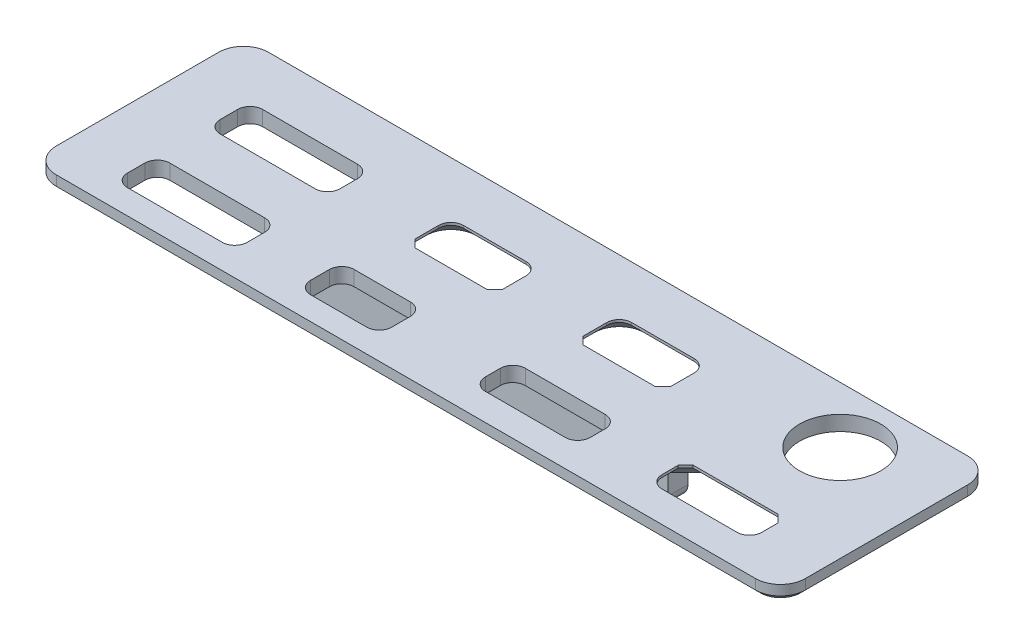
SolidWorks part; units mm, degrees
ref_plane "前视基准面" through (0, 0, 0) normal (0, 0, 1) x (1, 0, 0)
ref_plane "上视基准面" through (0, 0, 0) normal (0, 1, 0) x (1, 0, 0)
ref_plane "右视基准面" through (0, 0, 0) normal (1, 0, 0) x (0, 0, -1)
sketch "草图1" plane through (0, 0, 0) normal (0, 1, 0) x (1, 0, 0)
  line L1 (-30, 8.5) -> (30, 8.5)
  line L2 (-30, 8.5) -> (-30, -8.5)
  line L3 (-30, -8.5) -> (30, -8.5)
  line L4 (30, 8.5) -> (30, -8.5)
  line L5 (-30, 8.5) -> (30, -8.5) construction
  line L6 (-30, -8.5) -> (30, 8.5) construction
  point P0 (0, 0)
  dimension "D1" = 60
  dimension "D2" = 17
extrude "凸台-拉伸1" add sketch "草图1" along normal blind 1.2
sketch "草图4" plane through (0, 1.2, 0) normal (0, 1, 0) x (1, 0, 0)
  line L0 (-30, 8.5) -> (-30, -8.5) construction
  line L1 (-25.2717, 4.3) -> (-15.6717, 4.3)
  line L2 (-25.2717, 4.3) -> (-25.2717, 0.9)
  line L3 (-25.2717, 0.9) -> (-15.6717, 0.9)
  line L4 (-15.6717, 4.3) -> (-15.6717, 0.9)
  line L5 (-9.1829, 4.3) -> (-2.1829, 4.3)
  line L6 (-9.1829, 4.3) -> (-9.1829, 0.8)
  line L7 (-9.1829, 0.8) -> (-2.1829, 0.8)
  line L8 (-2.1829, 4.3) -> (-2.1829, 0.8)
  line L9 (4.2885, 4.3) -> (11.2885, 4.3)
  line L10 (4.2885, 4.3) -> (4.2885, 0.8)
  line L11 (4.2885, 0.8) -> (11.2885, 0.8)
  line L12 (11.2885, 4.3) -> (11.2885, 0.8)
  line L13 (17.05, -3.1348) -> (25.05, -3.1348)
  line L14 (17.05, -3.1348) -> (17.05, -6.0348)
  line L15 (17.05, -6.0348) -> (25.05, -6.0348)
  line L16 (25.05, -3.1348) -> (25.05, -6.0348)
  line L17 (3.2, -3.1348) -> (11.6, -3.1348)
  line L18 (3.2, -3.1348) -> (3.2, -6.3348)
  line L19 (3.2, -6.3348) -> (11.6, -6.3348)
  line L20 (11.6, -3.1348) -> (11.6, -6.3348)
  line L21 (-10.5, -3.1348) -> (-4, -3.1348)
  line L22 (-10.5, -3.1348) -> (-10.5, -6.6348)
  line L23 (-10.5, -6.6348) -> (-4, -6.6348)
  line L24 (-4, -3.1348) -> (-4, -6.6348)
  line L25 (-25.2717, -3.1348) -> (-15.6717, -3.1348)
  line L26 (-25.2717, -3.1348) -> (-25.2717, -6.5348)
  line L27 (-25.2717, -6.5348) -> (-15.6717, -6.5348)
  line L28 (-15.6717, -3.1348) -> (-15.6717, -6.5348)
  line L29 (30, 8.5) -> (-30, 8.5) construction
  line L31 (30, -8.5) -> (30, 8.5) construction
  line L32 (30, 8.5) -> (-30, 8.5) construction
  circle A0 centre (22.2985, 3.9832) radius 3.25
  dimension "D21" = 6.5
  dimension "D1" = 3.5
  dimension "D2" = 6.5
  dimension "D3" = 8.4
  dimension "D4" = 3.2
  dimension "D5" = 9.6
  dimension "D6" = 3.4
  dimension "D7" = 7
  dimension "D8" = 8
  dimension "D9" = 2.9
  dimension "D10" = 4.7283
  dimension "D11" = 7.6
  dimension "D12" = 11.6348
  dimension "D13" = 19.5
  dimension "D14" = 33.2
  dimension "D15" = 4.95
  dimension "D16" = 7
  dimension "D17" = 20.8171
  dimension "D18" = 34.2885
  dimension "D19" = 7.7015
  dimension "D20" = 4.5168
  dimension "D22" = 3.5
extrude "切除-拉伸1" cut sketch "草图4" against normal up to next
fillet "圆角2" radius 1 22 edges at (-25.2717, 0.6, -0.9) (-25.2717, 0.6, -4.3) (-15.6717, 0.6, -0.9) (-15.6717, 0.6, -4.3) (-2.1829, 0.6, -4.3) (-9.1829, 0.6, -4.3) (4.2885, 0.6, -4.3) (11.2885, 0.6, -4.3) (25.05, 0.6, 6.0348) (17.05, 0.6, 6.0348) (11.6, 0.6, 6.3348) (11.6, 0.6, 3.1348) (3.2, 0.6, 3.1348) (3.2, 0.6, 6.3348) (-4, 0.6, 6.6348) (-4, 0.6, 3.1348) (-10.5, 0.6, 3.1348) (-10.5, 0.6, 6.6348) (-15.6717, 0.6, 6.5348) (-15.6717, 0.6, 3.1348) (-25.2717, 0.6, 3.1348) (-25.2717, 0.6, 6.5348)
chamfer "倒角1" distance 0.6 angle 45 6 edges at (-9.1829, 0.6, -0.8) (-2.1829, 0.6, -0.8) (4.2885, 0.6, -0.8) (11.2885, 0.6, -0.8) (17.05, 0.6, 3.1348) (25.05, 0.6, 3.1348)
sketch "草图5" plane through (0, 0, 0) normal (0, -1, 0) x (1, 0, 0)
  line L0 (-30, -8.5) -> (-30, 8.5) construction
  line L1 (-13.9089, -3.3832) -> (-12.4089, -3.3832)
  line L2 (-13.9089, -3.3832) -> (-13.9089, 4.6168)
  line L3 (-13.9089, 4.6168) -> (-12.4089, 4.6168)
  line L4 (-12.4089, -3.3832) -> (-12.4089, 4.6168)
  line L5 (13.0911, -3.3832) -> (14.5911, -3.3832)
  line L6 (13.0911, -3.3832) -> (13.0911, 4.6168)
  line L7 (13.0911, 4.6168) -> (14.5911, 4.6168)
  line L8 (14.5911, -3.3832) -> (14.5911, 4.6168)
  line L9 (30, -8.5) -> (-30, -8.5) construction
  line L10 (30, 8.5) -> (30, -8.5) construction
  dimension "D1" = 1.5
  dimension "D2" = 8
  dimension "D3" = 1.5
  dimension "D4" = 8
  dimension "D5" = 16.0911
  dimension "D6" = 5.1168
  dimension "D7" = 5.1168
  dimension "D8" = 15.4089
extrude "凸台-拉伸2" add sketch "草图5" along normal blind 1.2
sketch "草图6" plane through (0, 0, 0) normal (0, -1, 0) x (1, 0, 0)
  line L0 (-13.9089, 4.6168) -> (-13.9089, -3.3832) construction
  line L1 (-13.9089, 2.1) -> (14.5911, 2.1)
  line L2 (-13.9089, 2.1) -> (-13.9089, 0.5)
  line L3 (-13.9089, 0.5) -> (14.5911, 0.5)
  line L4 (14.5911, 2.1) -> (14.5911, 0.5)
  line L5 (30, -8.5) -> (-30, -8.5) construction
  dimension "D1" = 1.6
  dimension "D2" = 9
extrude "凸台-拉伸3" add sketch "草图6" along normal blind 4
fillet "圆角3" radius 1 2 edges at (14.5911, -4, 1.3) (-13.9089, -4, 1.3)
chamfer "倒角2" distance 1 angle 45 4 edges at (13.8411, -1.2, -3.3832) (-13.1589, -1.2, -3.3832) (13.8411, -1.2, 4.6168) (-13.1589, -1.2, 4.6168)
chamfer "倒角4" distance 1 angle 45 24 edges at (11.2885, 0, -2.35) (10.9956, 0, -4.0071) (7.7885, 0, -4.3) (4.5814, 0, -4.0071) (10.9885, 0, -1.1) (4.2885, 0, -2.35) (4.5885, 0, -1.1) (7.7885, 0, -0.8) (-9.1829, 0, -2.35) (-2.1829, 0, -2.35) (-8.89, 0, -4.0071) (-2.4758, 0, -4.0071) (-5.6829, 0, -4.3) (-2.4829, 0, -1.1) (-8.8829, 0, -1.1) (-5.6829, 0, -0.8) (17.35, 0, 3.4348) (21.05, 0, 3.1348) (24.75, 0, 3.4348) (25.05, 0, 4.3848) (17.05, 0, 4.3848) (24.7571, 0, 5.7419) (17.3429, 0, 5.7419) (21.05, 0, 6.0348)
fillet "圆角4" radius 2 4 edges at (30, 0.6, 8.5) (30, 0.6, -8.5) (-30, 0.6, 8.5) (-30, 0.6, -8.5)
sketch "草图7" plane through (0, 0, 0) normal (0, -1, 0) x (1, 0, 0)
  line L0 (23, 8.5) -> (23, 11.0821)
  line L1 (-28, 8.5) -> (28, 8.5) construction
  line L2 (23, 11.0821) -> (22.5, 11.0821)
  line L3 (22.5, 11.0821) -> (22.5, 11.2821)
  line L4 (22.5, 11.2821) -> (23.1281, 10.5)
  line L5 (23.1281, 10.5) -> (23.8, 10.5)
  line L6 (23.8, 10.5) -> (23.8, 8.5)
  line L7 (23.8, 8.5) -> (23, 8.5)
  line L8 (30, 6.5) -> (30, -6.5) construction
  line L9 (-23.15, 8.5) -> (-23.15, 11.0821)
  line L10 (-23.15, 11.0821) -> (-22.65, 11.0821)
  line L11 (-22.65, 11.0821) -> (-22.65, 11.2821)
  line L12 (-22.65, 11.2821) -> (-23.4613, 10.5)
  line L13 (-23.4613, 10.5) -> (-23.95, 10.5)
  line L14 (-23.95, 10.5) -> (-23.95, 8.5)
  line L15 (-23.95, 8.5) -> (-23.15, 8.5)
  line L16 (-30, -6.5) -> (-30, 6.5) construction
  dimension "D1" = 0.8
  dimension "D2" = 6.2
  dimension "D3" = 0.5
  dimension "D4" = 0.2
  dimension "D5" = 2
  dimension "D6" = 6.05
chamfer "倒角5" distance 0.4 angle 45 8 edges at (0, 0, -8.5) (-29.4142, 0, -7.9142) (29.4142, 0, -7.9142) (-30, 0, 0) (30, 0, 0) (-29.4142, 0, 7.9142) (29.4142, 0, 7.9142) (0, 0, 8.5)
